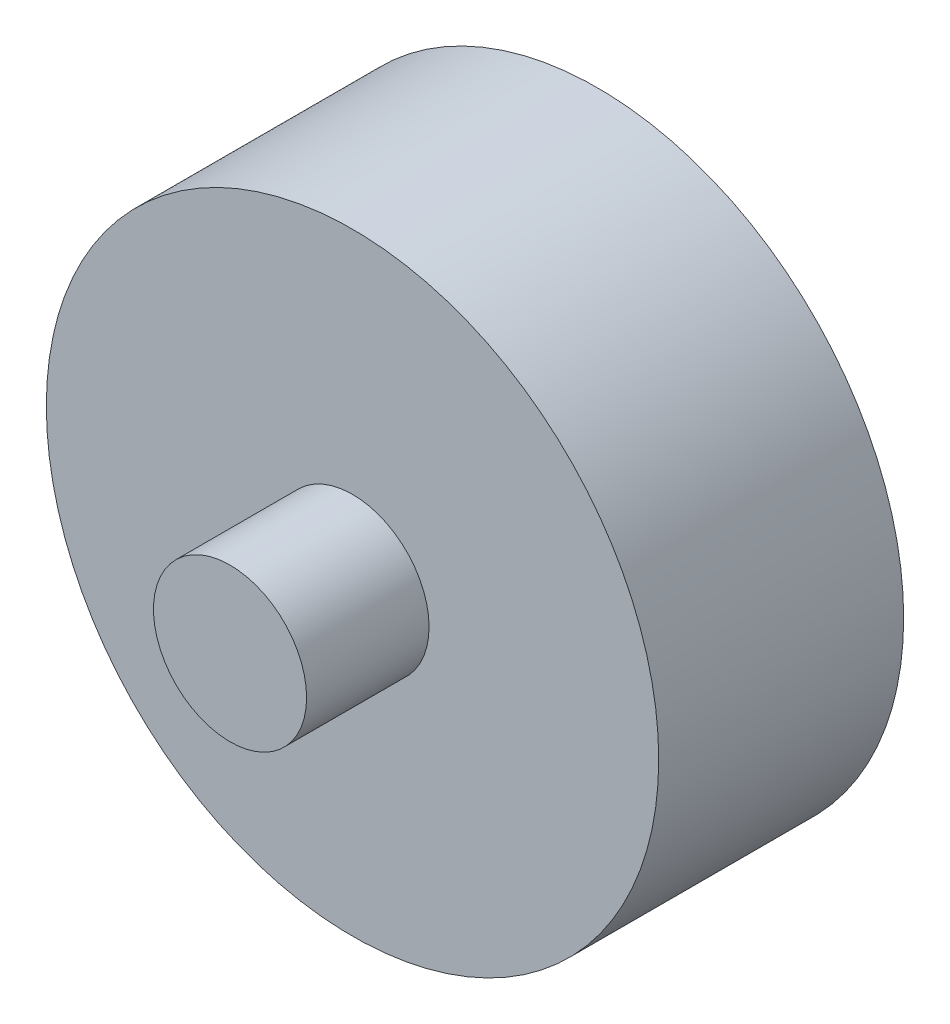
SolidWorks part; units mm, degrees
ref_plane "Front Plane" through (0, 0, 0) normal (0, 0, 1) x (1, 0, 0)
ref_plane "Top Plane" through (0, 0, 0) normal (0, 1, 0) x (1, 0, 0)
ref_plane "Right Plane" through (0, 0, 0) normal (1, 0, 0) x (0, 0, -1)
sketch "Sketch1" plane through (0, 0, 0) normal (0, 0, 1) x (1, 0, 0)
  circle A0 centre (10, 10) radius 10
  circle A1 centre (10, 10) radius 2.5
  dimension "D1" = 5
  dimension "D2" = 20
extrude "Boss-Extrude1" add sketch "Sketch1" along normal blind 12 contours A1 region at (10, 10, 0)
extrude "Boss-Extrude2" add sketch "Sketch1<3>" along normal blind 8
sketch "Sketch1<3>" plane through (0, 0, 0) normal (0, 0, 1) x (1, 0, 0) same geometry as "Sketch1"
